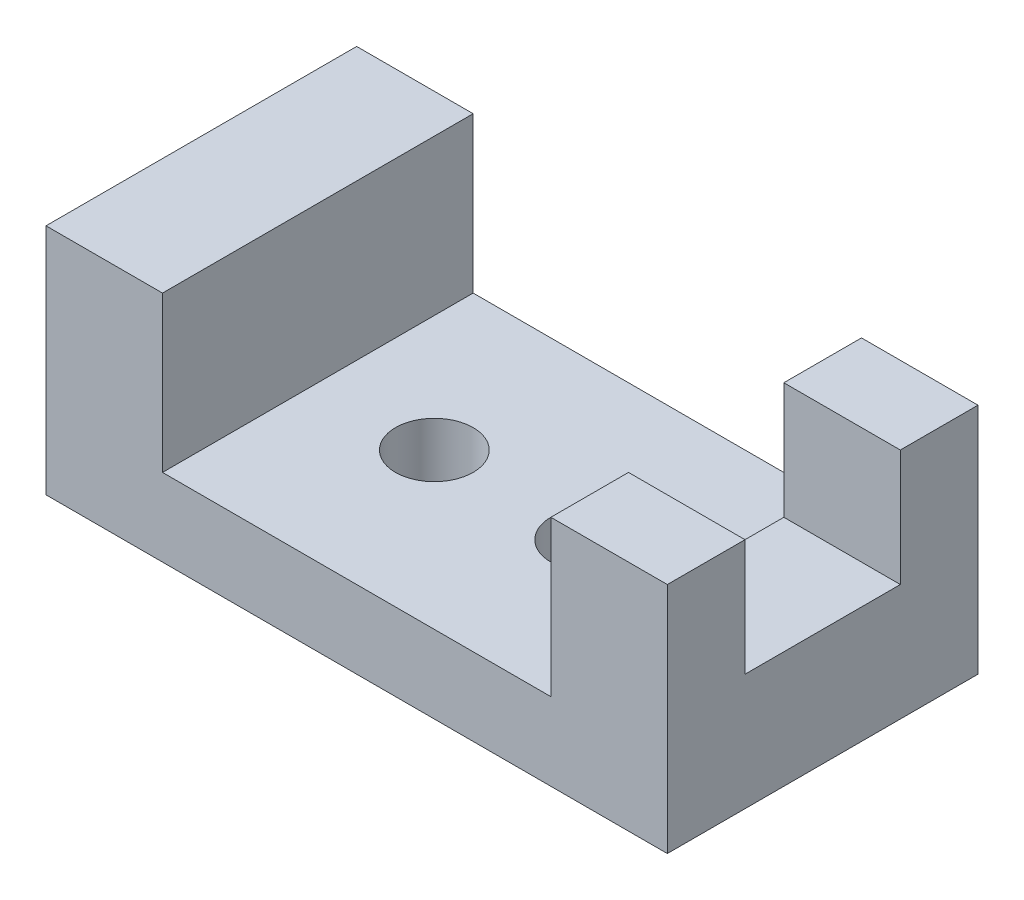
SolidWorks part; units mm, degrees
ref_plane "정면" through (0, 0, 0) normal (0, 0, 1) x (1, 0, 0)
ref_plane "윗면" through (0, 0, 0) normal (0, 1, 0) x (1, 0, 0)
ref_plane "우측면" through (0, 0, 0) normal (1, 0, 0) x (0, 0, -1)
sketch "스케치1" plane through (0, 0, 0) normal (0, 1, 0) x (1, 0, 0)
  line L0 (-36.0683, -13.5563) -> (-36.0683, -53.5563)
  line L1 (-51.0683, -53.5563) -> (28.9317, -53.5563)
  line L2 (-51.0683, -53.5563) -> (-51.0683, -13.5563)
  line L3 (-51.0683, -13.5563) -> (28.9317, -13.5563)
  line L4 (28.9317, -53.5563) -> (28.9317, -13.5563)
  line L5 (13.9317, -13.5563) -> (13.9317, -53.5563)
  line L6 (13.9317, -43.5563) -> (28.9317, -43.5563)
  line L7 (13.9317, -23.5563) -> (28.9317, -23.5563)
  circle A0 centre (-21.0683, -33.5563) radius 5
  circle A1 centre (-1.0683, -33.5563) radius 5
  point P16 (-23.044, -33.5563)
  point P17 (-1.5071, -33.5563)
  dimension "D1" = 80
  dimension "D2" = 40
  dimension "D3" = 15
  dimension "D4" = 15
  dimension "D5" = 10
  dimension "D6" = 10
  dimension "D7" = 15
  dimension "D8" = 15
extrude "보스-돌출2" add sketch "스케치1" along normal blind 30 contours L3 L2 L1 L0 | L6 L5 L1 L4 | L5 L7 L4 L3 region at (-43.5683, 0, 33.5563) region at (21.4317, 0, 18.5563) region at (21.4317, 0, 48.5563)
extrude "보스-돌출4" add sketch "스케치1<6>" along normal blind 15 contours L7 L5 L6 L4 region at (21.4317, 0, 33.5563)
sketch "스케치1<6>" plane through (0, 0, 0) normal (0, 1, 0) x (1, 0, 0) same geometry as "스케치1"
extrude "보스-돌출5" add sketch "스케치1<7>" along normal blind 10 contours L5 L3 L0 L1 A1 A0 region at (-11.0683, 0, 33.5563)
sketch "스케치1<7>" plane through (0, 0, 0) normal (0, 1, 0) x (1, 0, 0) same geometry as "스케치1"
